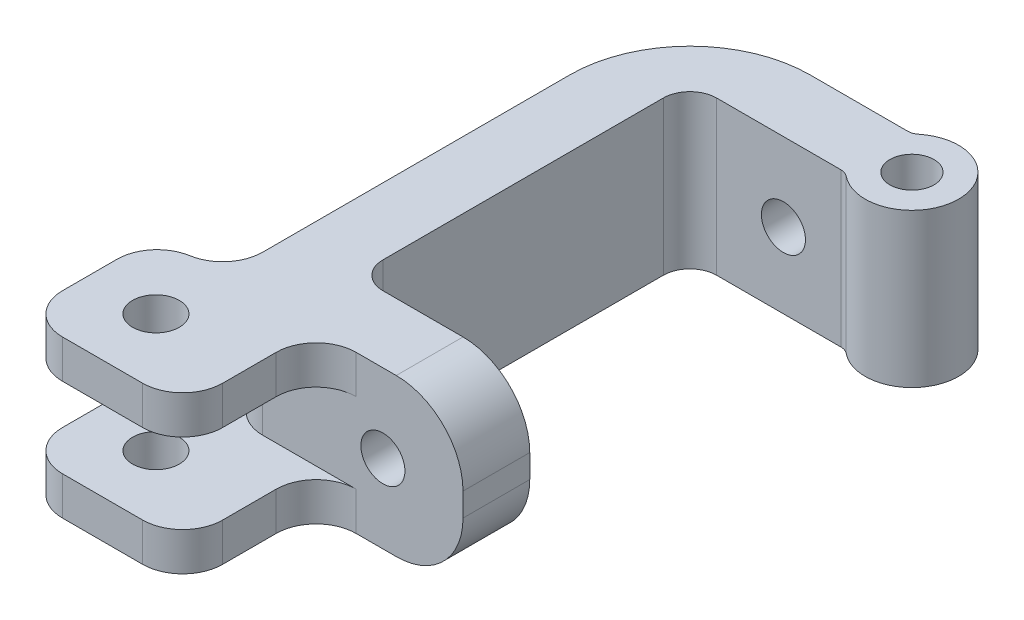
SolidWorks part; units mm, degrees
ref_plane "Front Plane" through (0, 0, 0) normal (0, 0, 1) x (1, 0, 0)
ref_plane "Top Plane" through (0, 0, 0) normal (0, 1, 0) x (1, 0, 0)
ref_plane "Right Plane" through (0, 0, 0) normal (1, 0, 0) x (0, 0, -1)
sketch "Sketch1" plane through (0, 0, 0) normal (0, 0, 1) x (1, 0, 0)
  line L2 (-10.125, 5.75) -> (10.125, 5.75)
  line L3 (-10.125, 5.75) -> (-10.125, -5.75)
  line L4 (-10.125, -5.75) -> (10.125, -5.75)
  line L5 (10.125, 5.75) -> (10.125, -5.75)
  line L6 (-10.125, 5.75) -> (10.125, -5.75) construction
  line L7 (-10.125, -5.75) -> (10.125, 5.75) construction
  point P2 (0, 0)
  dimension "D1" = 20.25
  dimension "D2" = 11.5
extrude "Boss-Extrude1" add sketch "Sketch1" along normal blind 5
sketch "Sketch2" plane through (0, 0, 5) normal (0, 0, 1) x (1, 0, 0)
  line L0 (-10.125, -5.75) -> (10.125, -5.75) construction
  line L1 (-10.125, 5.75) -> (-5.125, 5.75)
  line L2 (-10.125, 5.75) -> (-10.125, -5.75)
  line L3 (-10.125, -5.75) -> (-5.125, -5.75)
  line L4 (-5.125, 5.75) -> (-5.125, -5.75)
  dimension "D1" = 5
extrude "Boss-Extrude2" add sketch "Sketch2" along normal blind 25
sketch "Sketch3" plane through (0, 0, 30) normal (0, 0, 1) x (1, 0, 0)
  line L1 (-10.125, 5.75) -> (7.875, 5.75)
  line L2 (-10.125, 5.75) -> (-10.125, -6)
  line L3 (-10.125, -6) -> (7.875, -6)
  line L4 (7.875, 5.75) -> (7.875, -6)
  dimension "D1" = 18
  dimension "D2" = 18
extrude "Boss-Extrude3" add sketch "Sketch3" along normal blind 5
sketch "Sketch5" plane through (0, 0, 30) normal (0, 0, -1) x (-1, 0, 0)
  line L0 (-7.875, -0.125) -> (8.5, -0.125) construction
  line L1 (-7.875, -6) -> (-7.875, 5.75) construction
  line L3 (10.125, 5.75) -> (10.125, -6) construction
  circle A0 centre (-1.875, -0.125) radius 1.65
  dimension "D1" = 3.3
  dimension "D2" = 12
extrude "Cut-Extrude2" cut sketch "Sketch5" against normal through all both and the other way through all
fillet "Fillet1" radius 9 1 edges at (-10.125, 0, 0)
fillet "Fillet7" radius 5 2 edges at (7.875, -6, 32.5) (7.875, 5.75, 32.5)
sketch "Sketch10" plane through (0, -5.75, 0) normal (0, -1, 0) x (1, 0, 0)
  line L0 (10.125, 2.5) -> (6, 2.5) construction
  line L1 (10.125, 5) -> (10.125, 0) construction
  circle A0 centre (9, 2.5) radius 1.65
  circle A1 centre (9, 2.5) radius 3.5
  dimension "D1" = 3.3
  dimension "D3" = 7
extrude "Cut-Extrude4" cut sketch "Sketch10" against normal through all both and the other way through all contours A0
extrude "Boss-Extrude7" add sketch "Sketch10<4>" against normal blind 11.5 contours A1 | A0
sketch "Sketch10<4>" plane through (0, -5.75, 0) normal (0, -1, 0) x (1, 0, 0) same geometry as "Sketch10"
fillet "Fillet13" radius 1 2 edges at (6.5505, 0, 0) (6.5505, 0, 5)
fillet "Fillet16" radius 2 1 edges at (-5.125, 0, 5)
sketch "Sketch11" plane through (0, 0, 35) normal (0, 0, 1) x (1, 0, 0)
  line L0 (-10.125, 5.75) -> (-10.125, -6) construction
  line L1 (-10.125, -6) -> (2.875, -6) construction
  line L2 (-15.125, 2.875) -> (-3.125, 2.875)
  line L7 (-15.125, 5.75) -> (-3.125, 2.875) construction
  line L8 (-3.125, 5.75) -> (-15.125, 2.875) construction
  line L9 (2.875, 5.75) -> (-10.125, 5.75) construction
  line L10 (-15.125, -3.125) -> (-3.125, -6) construction
  line L11 (-15.125, 2.875) -> (-15.125, 5.75)
  line L12 (-15.125, 5.75) -> (-3.125, 5.75)
  line L13 (-3.125, 2.875) -> (-3.125, 5.75)
  line L14 (-15.125, -3.125) -> (-3.125, -3.125)
  line L15 (-15.125, -3.125) -> (-15.125, -6)
  line L16 (-15.125, -6) -> (-3.125, -6)
  line L17 (-3.125, -3.125) -> (-3.125, -6)
  line L18 (-3.125, -3.125) -> (-15.125, -6) construction
  point P4 (-10.125, 0)
  dimension "D3" = 12
  dimension "D1" = 5.75
  dimension "D2" = 0
  dimension "D4" = 12
  dimension "D5" = 6
  dimension "D6" = 5
  dimension "D7" = 5
extrude "Boss-Extrude8" add sketch "Sketch11" along normal blind 10 contours L11 L2 L13 L12 | L15 L14 L17 L16
sketch "Sketch12" plane through (0, 5.75, 0) normal (0, 1, 0) x (1, 0, 0)
  line L0 (-15.125, -35) -> (-10.125, -35) construction
  line L1 (-15.125, -45) -> (-15.125, -35) construction
  circle A0 centre (-10.125, -40) radius 1.75
  dimension "D1" = 3.5
  dimension "D2" = 5
  dimension "D3" = 5
extrude "Cut-Extrude5" cut sketch "Sketch12" along normal through all and the other way through all contours A0
fillet "Fillet17" radius 3 8 edges at (-3.125, 4.3125, 35) (-3.125, 4.3125, 45) (-15.125, 4.3125, 45) (-10.125, 4.3125, 35) (-3.125, -4.5625, 35) (-3.125, -4.5625, 45) (-15.125, -4.5625, 45) (-10.125, -4.5625, 35)
fillet "Fillet18" radius 3 2 edges at (-15.125, 4.3125, 35) (-15.125, -4.5625, 35)
fillet "Fillet19" radius 3 1 edges at (-10.125, -0.125, 35)
fillet "Fillet20" radius 2 1 edges at (-5.125, 0, 30)
